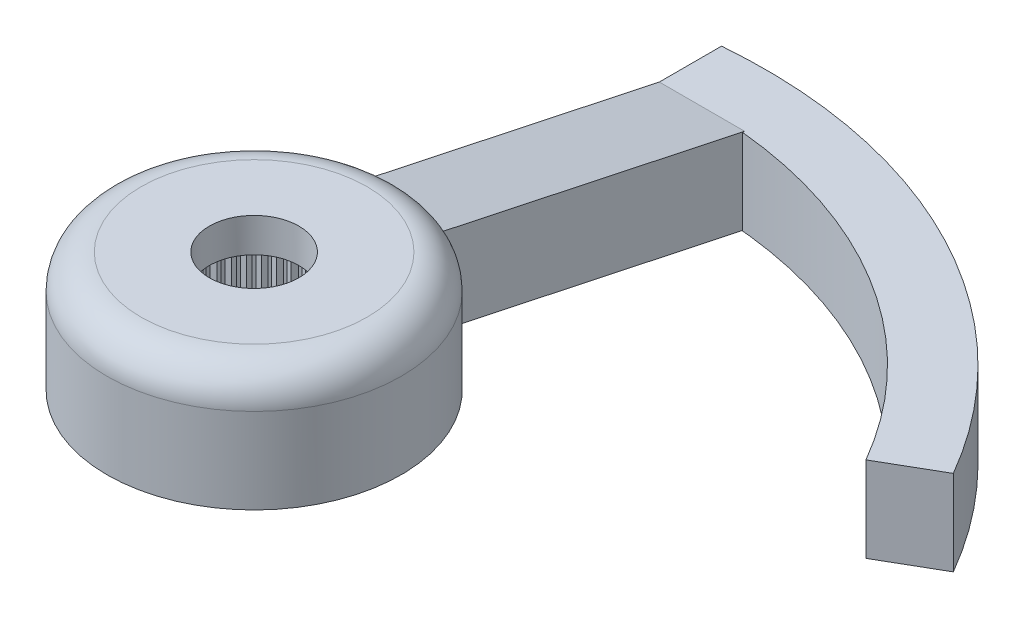
SolidWorks part; units mm, degrees
material "PVC Rígido"
ref_plane "Plano frontal" through (0, 0, 0) normal (0, 0, 1) x (1, 0, 0)
ref_plane "Plano superior" through (0, 0, 0) normal (0, 1, 0) x (1, 0, 0)
ref_plane "Plano direito" through (0, 0, 0) normal (1, 0, 0) x (0, 0, -1)
sketch "Esboço1" plane through (0, 0, 0) normal (0, 1, 0) x (1, 0, 0)
  line L0 (0, 0) -> (-14.05, 0) construction
  line L1 (-14.1591, 1.997) -> (-2.2091, 2.65)
  line L2 (-2.2091, -2.65) -> (-14.1591, -1.997)
  arc A0 (-2.2091, -2.65) -> (-2.2091, 2.65) centre (0, 0) ccw
  arc A1 (-14.1591, 1.997) -> (-14.1591, -1.997) centre (-14.05, 0) ccw
  dimension "D1" = 6.9
  dimension "D2" = 4
  dimension "D3" = 19.5
  dimension "D4" = 5.3
extrude "Ressalto-extrusão1" add sketch "Esboço1" against normal blind 1.4
sketch "Esboço2" plane through (0, -1.4, 0) normal (0, -1, 0) x (1, 0, 0)
  arc A0 (-2.2091, -2.65) -> (-2.2091, 2.65) centre (0, 0) ccw construction
  circle A1 centre (0, 0) radius 3.45
extrude "Ressalto-extrusão2" add sketch "Esboço2" along normal offset from surface (2.4 mm away) 3.8 up to face at (-7.242, 0, 0)
hole_wizard "Furo4" positions "Esboço9" profile "Esboço10" legacy end condition through all
sketch "Esboço9" plane through (0, 0, 0) normal (0, 1, 0) x (1, 0, 0)
  line L1 (-14.45, 0) -> (0, 0) construction
  arc A2 (-14.1591, 1.997) -> (-14.1591, -1.997) centre (-14.05, 0) ccw construction
  point P0 (-14.45, 0)
  point P19 (-16.05, 0)
  dimension "D1" = 1.6
sketch "Esboço10" plane through (-14.45, 0, 0) normal (1, 0, 0) x (0, 0, 1)
  line L0 (0, 0) -> (0, 3.8)
  line L1 (0, 3.8) -> (0.6, 3.8)
  line L2 (0.6, 3.8) -> (0.6, 0)
  line L3 (0.6, 0) -> (0, 0)
  line L4 (0, 110) -> (0, -10) construction
  dimension "Diameter" = 1.2
  dimension "Depth" = 3.8
pattern_linear "Padrão linear1" count 6 spacing 2 along (1, 0, 0) of "Furo4"
hole_wizard "Furo1" positions "Esboço3" profile "Esboço4" legacy
sketch "Esboço3" plane through (0, -3.8, 0) normal (0, -1, 0) x (-1, 0, 0)
  point P0 (0, 0)
sketch "Esboço4" plane through (0, -3.8, 0) normal (1, 0, 0) x (0, 0, -1)
  line L0 (0, 0) -> (0, 2)
  line L1 (0, 2) -> (2.475, 2)
  line L2 (2.475, 2) -> (2.475, 0)
  line L3 (2.475, 0) -> (0, 0)
  line L4 (0, 110) -> (0, -10) construction
  dimension "Diameter" = 4.95
  dimension "Depth" = 2
hole_wizard "Furo2" positions "Esboço5" profile "Esboço6" legacy
sketch "Esboço5" plane through (0, 0, 0) normal (0, 1, 0) x (1, 0, 0)
  point P0 (0, 0)
sketch "Esboço6" plane through (0, 0, 0) normal (1, 0, 0) x (0, 0, 1)
  line L0 (0, 0) -> (0, 1)
  line L1 (0, 1) -> (2.3, 1)
  line L2 (2.3, 1) -> (2.3, 0)
  line L3 (2.3, 0) -> (0, 0)
  line L4 (0, 110) -> (0, -10) construction
  dimension "Diameter" = 4.6
  dimension "Depth" = 1
hole_wizard "Furo3" positions "Esboço7" profile "Esboço8" legacy end condition through all
sketch "Esboço7" plane through (0, 0, 0) normal (0, 1, 0) x (1, 0, 0)
  point P0 (0, 0)
sketch "Esboço8" plane through (0, 0, 0) normal (1, 0, 0) x (0, 0, 1)
  line L0 (0, 0) -> (0, 3.8)
  line L1 (0, 3.8) -> (1.05, 3.8)
  line L2 (1.05, 3.8) -> (1.05, 0)
  line L3 (1.05, 0) -> (0, 0)
  line L4 (0, 110) -> (0, -10) construction
  dimension "Diameter" = 2.1
  dimension "Depth" = 3.8
sketch "Esboço11" plane through (0, -3.8, 0) normal (0, -1, 0) x (1, 0, 0)
  line L0 (-0.0981, 2.4731) -> (0, 2.375)
  line L1 (0, 2.375) -> (0.0981, 2.4731)
  line L2 (0, 0) -> (0, 2.475) construction
  circle A0 centre (0, 0) radius 2.375 construction
  circle A1 centre (0, 0) radius 2.475
  arc A2 (0.0981, 2.4731) -> (-0.0981, 2.4731) centre (0, 0) ccw
  dimension "D3" = 4.75
  dimension "D2" = 0.1
  dimension "D1" = 0
extrude "Ressalto-extrusão3" add sketch "Esboço11" against normal up to surface (2 mm away) up to face at (0, -1.8, 1.05)
pattern_circular "PadrãoCircular1" count 60 over 360 about axis through (0, -1.4, 0) along (0, 1, 0) of "Ressalto-extrusão3"
sketch "Croquis1" plane through (0, -1.4, 0) normal (0, -1, 0) x (1, 0, 0)
  line L0 (-14.1591, 1.997) -> (-2.2091, 2.65) construction
  line L1 (-14.1591, 1.997) -> (-2.2091, 2.65)
  line L2 (-2.2091, -2.65) -> (-14.1591, -1.997) construction
  line L3 (-2.2091, -2.65) -> (-14.1591, -1.997)
  arc A0 (-2.2091, 2.65) -> (-2.2091, -2.65) centre (0, 0) ccw construction
  arc A1 (-14.1591, 1.997) -> (-14.1591, -1.997) centre (-14.05, 0) ccw construction
  arc A2 (-2.2091, 2.65) -> (-2.2091, -2.65) centre (0, 0) ccw
  arc A3 (-14.1591, 1.997) -> (-14.1591, -1.997) centre (-14.05, 0) ccw
extrude "Eliminado brazo anterior" cut sketch "Croquis1" against normal up to next
sketch "Croquis4" plane through (0, 0, 0) normal (0, 1, 0) x (1, 0, 0)
  circle A0 centre (0, 0) radius 3.45 construction
  circle A1 centre (0, 0) radius 3.45
extrude "Cortar-Extruir2" cut sketch "Croquis4" against normal blind 1
fillet "Redondeo1" radius 0.8 1 edges at (0, -1, 3.45)
sketch "Croquis9" plane through (0, 0, 0) normal (1, 0, 0) x (0, 0, -1)
  line L0 (10.5, -5.3) -> (3.45, -3.8)
  line L1 (10.5, -5.3) -> (10.5, -3.3)
  line L2 (3.45, -3.8) -> (3.0334, -3.8)
  line L3 (0, 0) -> (0, -5.3) construction
  line L4 (-10.5, -5.3) -> (10.5, -5.3)
  line L5 (3.45, -1.8) -> (10.5, -3.3)
  line L6 (-3.45, -3.8) -> (3.45, -3.8) construction
  line L10 (3.0334, -3.8) -> (3.0334, -1.8)
  line L11 (3.0334, -1.8) -> (3.45, -1.8)
  point P6 (3.45, -3.8)
  point P8 (3.45, -1.8)
  point P12 (0, -5.3)
  dimension "D1" = 10.5
  dimension "D2" = 1.5
extrude "Saliente-Extruir3" add sketch "Croquis9" along normal blind 1 and the other way blind 1 separate body contours L0 L1 L5 region at (0, -3.5082, -6.7667)
ref_plane "Plano1" through (0, -5.3, 0) normal (0, -1, 0) x (-1, 0, 0)
sketch "Croquis10" plane through (0, -5.3, 0) normal (0, -1, 0) x (-1, 0, 0)
  line L0 (1, 10.4523) -> (1, 10.5)
  line L4 (1, 10.5) -> (1, 11.9583)
  line L5 (0, 0) -> (-12, 0) construction
  line L6 (0, 0) -> (-10.3923, 6) construction
  line L7 (-10.3923, 6) -> (-9.0933, 5.25)
  arc A0 (1, 10.4523) -> (-9.0933, 5.25) centre (0, 0) ccw
  arc A1 (1, 11.9583) -> (-10.3923, 6) centre (0, 0) ccw
  dimension "D1" = 24
  dimension "D2" = 30
extrude "Saliente-Extruir4" add sketch "Croquis10" against normal blind 2
